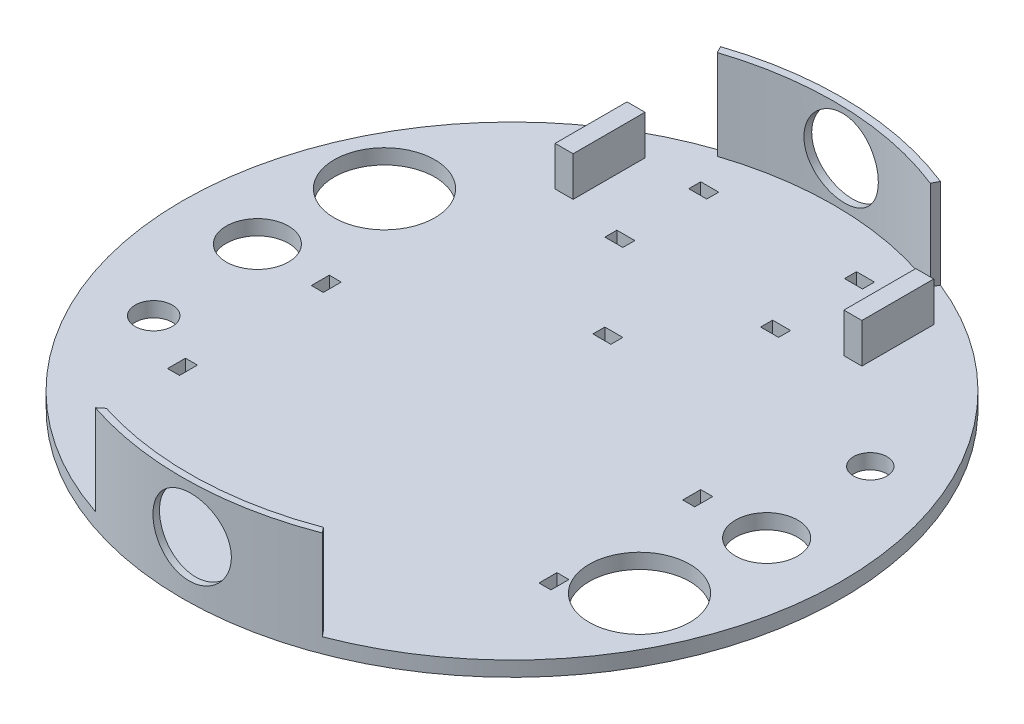
SolidWorks part; units mm, degrees
note: The reader was unsure of these and kept them because the rebuilt part matched: shared geometry of "Sketch3<4>".
ref_plane "Front Plane" through (0, 0, 0) normal (0, 0, 1) x (1, 0, 0)
ref_plane "Top Plane" through (0, 0, 0) normal (0, 1, 0) x (1, 0, 0)
ref_plane "Right Plane" through (0, 0, 0) normal (1, 0, 0) x (0, 0, -1)
sketch "Sketch1" plane through (0, 0, 0) normal (0, 1, 0) x (1, 0, 0)
  circle A0 centre (0, 0) radius 69.85
extrude "Boss-Extrude1" add sketch "Sketch1" along normal blind 3.175
sketch "Sketch2" plane through (0, 3.175, 0) normal (0, 1, 0) x (1, 0, 0)
  line L0 (53.975, 0) -> (-53.975, 0) construction
  line L1 (51.7955, 24.1526) -> (-51.7955, -24.1526) construction
  line L2 (0, 0) -> (50.6445, -23.6159) construction
  line L3 (0, 0) -> (-50.6445, 23.6159) construction
  circle A0 centre (-53.975, 0) radius 6.604
  circle A1 centre (53.975, 0) radius 6.604
  circle A2 centre (-51.7955, -24.1526) radius 3.937
  circle A3 centre (51.7955, 24.1526) radius 3.556
  circle A4 centre (50.6445, -23.6159) radius 10.668
  circle A5 centre (-50.6445, 23.6159) radius 10.668
  point P4 (0, 0)
  point P8 (0, 0)
extrude "Cut-Extrude1" cut sketch "Sketch2" against normal blind 3.175
sketch "Sketch3" plane through (0, 3.175, 0) normal (0, 1, 0) x (1, 0, 0)
  line L0 (39.37, 0) -> (-39.37, 0) construction
  line L1 (-39.37, 0) -> (-39.37, -30.48) construction
  line L2 (39.37, 0) -> (39.37, -30.48) construction
  line L3 (0, 0) -> (0, 20.32) construction
  line L4 (-38.1, -1.905) -> (-40.64, -1.905)
  line L5 (-38.1, -1.905) -> (-38.1, 1.905)
  line L6 (-38.1, 1.905) -> (-40.64, 1.905)
  line L7 (-40.64, -1.905) -> (-40.64, 1.905)
  line L8 (-38.1, -1.905) -> (-40.64, 1.905) construction
  line L9 (-38.1, 1.905) -> (-40.64, -1.905) construction
  line L10 (-38.1, -32.385) -> (-40.64, -32.385)
  line L11 (-38.1, -32.385) -> (-38.1, -28.575)
  line L12 (-38.1, -28.575) -> (-40.64, -28.575)
  line L13 (-40.64, -32.385) -> (-40.64, -28.575)
  line L14 (-38.1, -32.385) -> (-40.64, -28.575) construction
  line L15 (-38.1, -28.575) -> (-40.64, -32.385) construction
  line L16 (40.64, -32.385) -> (38.1, -32.385)
  line L17 (40.64, -32.385) -> (40.64, -28.575)
  line L18 (40.64, -28.575) -> (38.1, -28.575)
  line L19 (38.1, -32.385) -> (38.1, -28.575)
  line L20 (40.64, -32.385) -> (38.1, -28.575) construction
  line L21 (40.64, -28.575) -> (38.1, -32.385) construction
  line L22 (40.64, -1.905) -> (38.1, -1.905)
  line L23 (40.64, -1.905) -> (40.64, 1.905)
  line L24 (40.64, 1.905) -> (38.1, 1.905)
  line L25 (38.1, -1.905) -> (38.1, 1.905)
  line L26 (40.64, -1.905) -> (38.1, 1.905) construction
  line L27 (40.64, 1.905) -> (38.1, -1.905) construction
  line L28 (0, 0) -> (0, -50.8) construction
  line L29 (0, 0) -> (0, 48.26) construction
  line L30 (1.905, 19.05) -> (-1.905, 19.05)
  line L31 (1.905, 19.05) -> (1.905, 21.59)
  line L32 (1.905, 21.59) -> (-1.905, 21.59)
  line L33 (-1.905, 19.05) -> (-1.905, 21.59)
  line L34 (1.905, 19.05) -> (-1.905, 21.59) construction
  line L35 (1.905, 21.59) -> (-1.905, 19.05) construction
  line L36 (1.905, -52.07) -> (-1.905, -52.07)
  line L37 (1.905, -52.07) -> (1.905, -49.53)
  line L38 (1.905, -49.53) -> (-1.905, -49.53)
  line L39 (-1.905, -52.07) -> (-1.905, -49.53)
  line L40 (1.905, -52.07) -> (-1.905, -49.53) construction
  line L41 (1.905, -49.53) -> (-1.905, -52.07) construction
  line L42 (28.702, 48.26) -> (-28.702, 48.26) construction
  line L43 (-28.702, 56.896) -> (-28.702, 39.624) construction
  line L44 (28.702, 39.624) -> (28.702, 56.896) construction
  line L46 (-28.702, 56.896) -> (-32.512, 56.896)
  line L50 (28.702, 56.896) -> (32.512, 56.896)
  line L53 (16.51, 48.26) -> (-16.51, 48.26) construction
  line L54 (-16.51, 57.15) -> (-16.51, 39.37) construction
  line L55 (16.51, 57.15) -> (16.51, 39.37) construction
  line L56 (-28.702, 56.896) -> (-28.702, 41.656)
  line L57 (-14.605, 55.88) -> (-18.415, 55.88)
  line L58 (-14.605, 55.88) -> (-14.605, 58.42)
  line L59 (-14.605, 58.42) -> (-18.415, 58.42)
  line L60 (-18.415, 55.88) -> (-18.415, 58.42)
  line L61 (-14.605, 55.88) -> (-18.415, 58.42) construction
  line L62 (-14.605, 58.42) -> (-18.415, 55.88) construction
  line L63 (18.415, 55.88) -> (14.605, 55.88)
  line L64 (18.415, 55.88) -> (18.415, 58.42)
  line L65 (18.415, 58.42) -> (14.605, 58.42)
  line L66 (14.605, 55.88) -> (14.605, 58.42)
  line L67 (18.415, 55.88) -> (14.605, 58.42) construction
  line L68 (18.415, 58.42) -> (14.605, 55.88) construction
  line L69 (18.415, 38.1) -> (14.605, 38.1)
  line L70 (18.415, 38.1) -> (18.415, 40.64)
  line L71 (18.415, 40.64) -> (14.605, 40.64)
  line L72 (14.605, 38.1) -> (14.605, 40.64)
  line L73 (18.415, 38.1) -> (14.605, 40.64) construction
  line L74 (18.415, 40.64) -> (14.605, 38.1) construction
  line L75 (-14.605, 38.1) -> (-18.415, 38.1)
  line L76 (-14.605, 38.1) -> (-14.605, 40.64)
  line L77 (-14.605, 40.64) -> (-18.415, 40.64)
  line L78 (-18.415, 38.1) -> (-18.415, 40.64)
  line L79 (-14.605, 38.1) -> (-18.415, 40.64) construction
  line L80 (-14.605, 40.64) -> (-18.415, 38.1) construction
  line L81 (-32.512, 56.896) -> (-32.512, 41.656)
  line L82 (-32.512, 41.656) -> (-28.702, 41.656)
  line L86 (28.702, 56.896) -> (28.702, 41.656)
  line L87 (32.512, 56.896) -> (32.512, 41.656)
  line L88 (32.512, 41.656) -> (28.702, 41.656)
  point P5 (0, 0)
  point P37 (0, 48.26)
  point P40 (-28.702, 48.26)
  point P42 (28.702, 48.26)
  point P49 (0, 48.26)
  point P52 (-16.51, 48.26)
  point P55 (16.51, 48.26)
extrude "Boss-Extrude2" add sketch "Sketch3" along normal blind 8.382 contours L46 L81 L82 L56 | L86 L50 L87 L88
extrude "Cut-Extrude2" cut sketch "Sketch3<4>" against normal blind 8.382 contours L12 L13 L10 L11 | L6 L7 L4 L5 | L38 L39 L36 L37 | L24 L25 L22 L23 | L18 L19 L16 L17 | L32 L33 L30 L31 | L63 L66 L65 L64 | L59 L60 L57 L58 | L71 L72 L69 L70 | L77 L78 L75 L76
sketch "Sketch3<4>" plane through (0, 3.175, 0) normal (0, 1, 0) x (1, 0, 0) same geometry as "Sketch3"
sketch "Sketch4" plane through (0, 3.175, 0) normal (0, 1, 0) x (1, 0, 0)
  line L1 (28.702, 56.896) -> (32.512, 56.896)
  line L2 (28.702, 56.896) -> (28.702, 41.656)
  line L3 (28.702, 41.656) -> (32.512, 41.656)
  line L4 (32.512, 56.896) -> (32.512, 41.656)
extrude "Boss-Extrude4" add sketch "Sketch4" along normal blind 8.382
sketch "Sketch5" plane through (0, 3.175, 0) normal (0, 1, 0) x (1, 0, 0)
  line L0 (-22.0602, 66.2749) -> (-21.3313, 64.8411)
  line L1 (25.2369, 63.4231) -> (25.9741, 64.8411)
  line L2 (-22.0602, -66.2749) -> (-20.7649, -65.218)
  line L3 (25.0126, -65.218) -> (24.0797, -64.0683)
  arc A0 (-22.0602, 66.2749) -> (25.9741, 64.8411) centre (0, 0) cw
  circle A1 centre (0, 0) radius 69.85 construction
  arc A2 (-21.3313, 64.8411) -> (25.2369, 63.4231) centre (0, 0) cw
  arc A3 (-22.0602, -66.2749) -> (25.0126, -65.218) centre (0, 0) ccw
  arc A4 (-20.7649, -65.218) -> (24.0797, -64.0683) centre (0, 0) ccw
extrude "Boss-Extrude5" add sketch "Sketch5" along normal blind 19.05
ref_plane "Plane1" through (2.0841, 22.225, -69.8189) normal (0.0298, 0, -0.9996) x (-0.9996, 0, -0.0298)
sketch "Sketch6" plane through (2.0841, 22.225, -69.8189) normal (0.0298, 0, -0.9996) x (-0.9996, 0, -0.0298)
  circle A0 centre (0, -9.3868) radius 8.128
extrude "Cut-Extrude3" cut sketch "Sketch6" against normal blind 19.05
ref_plane "Plane2" through (1.5679, 22.225, 69.8324) normal (0.0224, 0, 0.9997) x (0.9997, 0, -0.0224)
sketch "Sketch7" plane through (1.5679, 22.225, 69.8324) normal (0.0224, 0, 0.9997) x (0.9997, 0, -0.0224)
  line L0 (0, 0) -> (0, -10.16) construction
  line L1 (23.5423, 0) -> (-23.5423, 0) construction
  circle A0 centre (0, -10.16) radius 8.128
extrude "Cut-Extrude4" cut sketch "Sketch7" against normal blind 19.05
